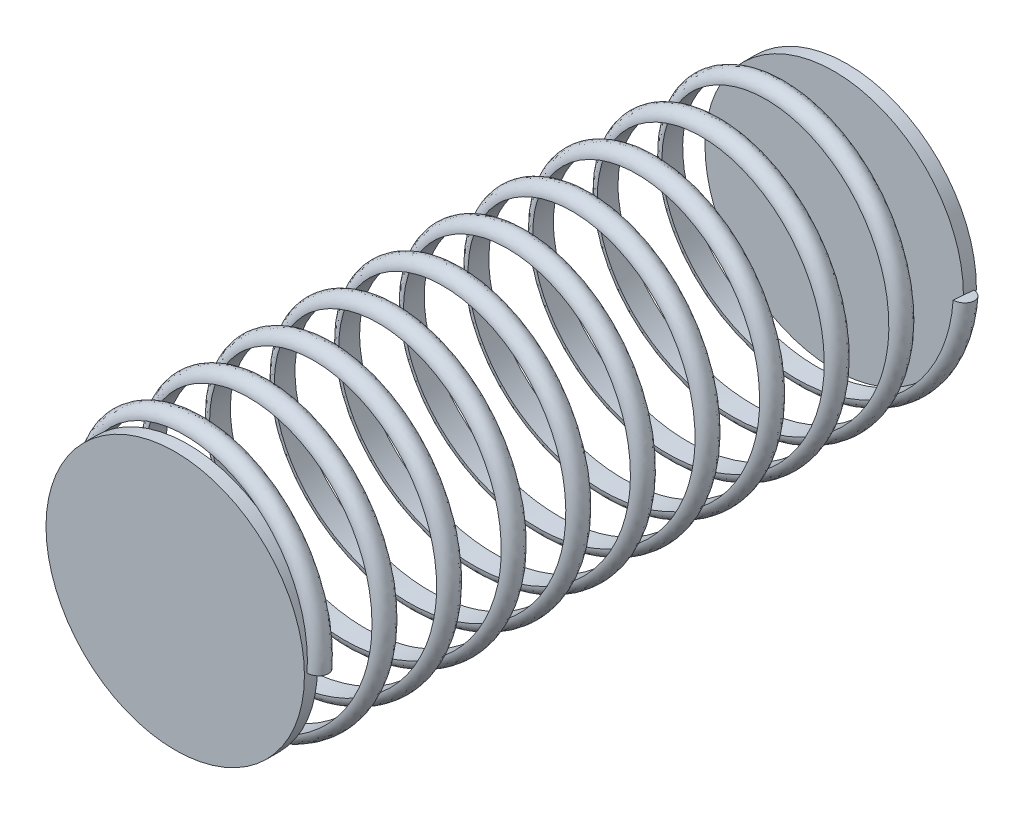
SolidWorks part; units mm, degrees
ref_plane "前视基准面" through (0, 0, 0) normal (0, 0, 1) x (1, 0, 0)
ref_plane "上视基准面" through (0, 0, 0) normal (0, 1, 0) x (1, 0, 0)
ref_plane "右视基准面" through (0, 0, 0) normal (1, 0, 0) x (0, 0, -1)
sketch "草图1" plane through (0, 0, 0) normal (0, 0, 1) x (1, 0, 0)
  circle A0 centre (0, 0) radius 10
curve "螺旋线/涡状线1" pitch 5 height 50 radius 10 left hand yes centre (0, 0, 0) axis (0, 0, 1) start towards (1, 0, 0)
sketch "草图2" plane through (0, 0, 0) normal (0, 1, 0) x (1, 0, 0)
  circle A0 centre (20.028, 0) radius 0.4248
sweep "扫描1" add path "螺旋线/涡状线1" circular profile diameter 1.6 parameters "D3"=1.6
extrude "凸台-拉伸3" add sketch "草图1<4>" against normal blind 1 and the other way blind 51
sketch "草图1<4>" plane through (0, 0, 0) normal (0, 0, 1) x (1, 0, 0) same geometry as "草图1"
extrude "切除-拉伸1" cut sketch "草图1<5>" along normal blind 50
sketch "草图1<5>" plane through (0, 0, 0) normal (0, 0, 1) x (1, 0, 0) same geometry as "草图1"
